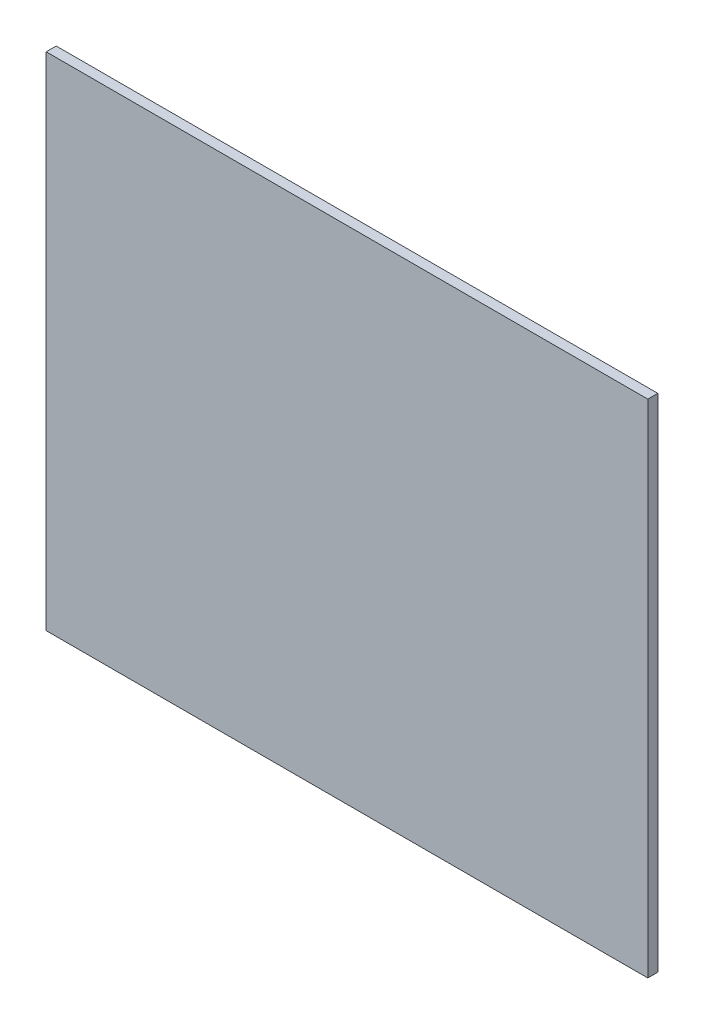
SolidWorks part; units mm, degrees
ref_plane "Plan de face" through (0, 0, 0) normal (0, 0, 1) x (1, 0, 0)
ref_plane "Plan de dessus" through (0, 0, 0) normal (0, 1, 0) x (1, 0, 0)
ref_plane "Plan de droite" through (0, 0, 0) normal (1, 0, 0) x (0, 0, -1)
sketch "Esquisse1" plane through (0, 0, 0) normal (0, 0, 1) x (1, 0, 0)
  line L0 (0, 500) -> (0, 0) construction
  line L1 (0, 0) -> (600, 0)
  line L2 (0, 0) -> (0, 500)
  line L3 (0, 500) -> (600, 500)
  line L4 (600, 0) -> (600, 500)
  dimension "D1" = 600
extrude "Boss.-Extru.1" add sketch "Esquisse1" along normal blind 10
